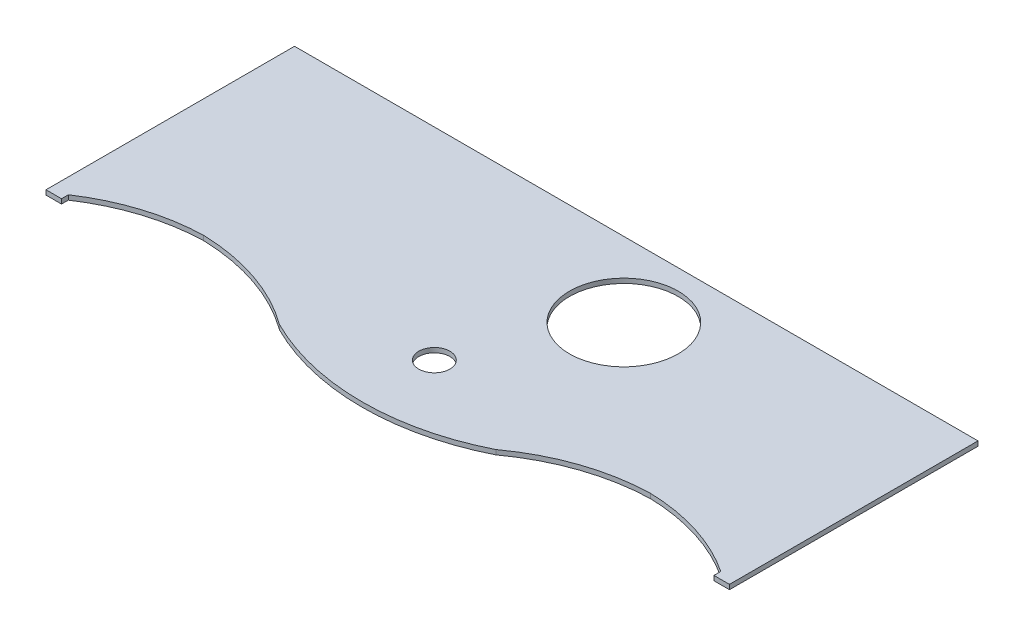
SolidWorks part; units mm, degrees
ref_plane "Front Plane" through (0, 0, 0) normal (0, 0, 1) x (1, 0, 0)
ref_plane "Top Plane" through (0, 0, 0) normal (0, 1, 0) x (1, 0, 0)
ref_plane "Right Plane" through (0, 0, 0) normal (1, 0, 0) x (0, 0, -1)
ref_plane "Plane1" through (0, 22.5, 0) normal (0, 1, 0) x (1, 0, 0)
ref_plane "Plane2" through (0, 24, 0) normal (0, 1, 0) x (1, 0, 0)
sketch "Sketch2" plane through (0, 22.5, 0) normal (0, 1, 0) x (1, 0, 0)
  line L0 (0, -100) -> (0, 70) construction
  line L7 (71.9147, -28) -> (71.9147, -17.3273) construction
  line L8 (-110, 50) -> (110, 50)
  line L9 (-105, -27.799) -> (-105, -30.0025)
  line L10 (-105, -30.0025) -> (-110, -30)
  line L11 (-110, -30) -> (-110, 50)
  line L12 (110, 50) -> (110, -30)
  line L13 (110, -30) -> (105, -30.0025)
  line L14 (105, -30.0025) -> (105, -27.799)
  line L15 (-34.8399, -30) -> (34.8399, -30) construction
  line L17 (105, -27.799) -> (110, -27.799) construction
  arc A0 (-105, -27.799) -> (-71.9147, -17.3273) centre (-70.2175, -80.192) cw
  arc A1 (-71.9147, -17.3273) -> (-105, -27.799) centre (-70.2175, -80.192) ccw construction
  arc A2 (-71.9147, -17.3273) -> (-34.8399, -30) centre (-73.6989, -83.1159) cw
  arc A3 (-34.8399, -30) -> (-71.9147, -17.3273) centre (-73.6989, -83.1159) ccw construction
  arc A6 (34.8399, -30) -> (71.9147, -17.3273) centre (73.6989, -83.1159) cw
  arc A7 (71.9147, -17.3273) -> (34.8399, -30) centre (73.6989, -83.1159) ccw construction
  arc A8 (71.9147, -17.3273) -> (105, -27.799) centre (70.2175, -80.192) cw
  arc A9 (105, -27.799) -> (71.9147, -17.3273) centre (70.2175, -80.192) ccw construction
  arc A11 (105, -27.799) -> (71.9147, -17.3273) centre (70.2175, -80.192) ccw construction
  circle A12 centre (20, 26) radius 17.5
  circle A13 centre (20, 26) radius 17.5 construction
  circle A14 centre (0, -15) radius 5
  circle A15 centre (0, -15) radius 5 construction
  arc A16 (-34.8399, -30) -> (34.8399, -30) centre (0, 39.341) ccw
  arc A17 (-34.8399, -30) -> (34.8399, -30) centre (0, 39.341) ccw construction
  point P0 (0, 10.0408)
  point P28 (0, 0)
  point P51 (0, 0)
  point P55 (105, -30.0025)
extrude "Boss-Extrude2" add sketch "Sketch2" along normal up to surface (1.5 mm away) up to plane "Plane2"
